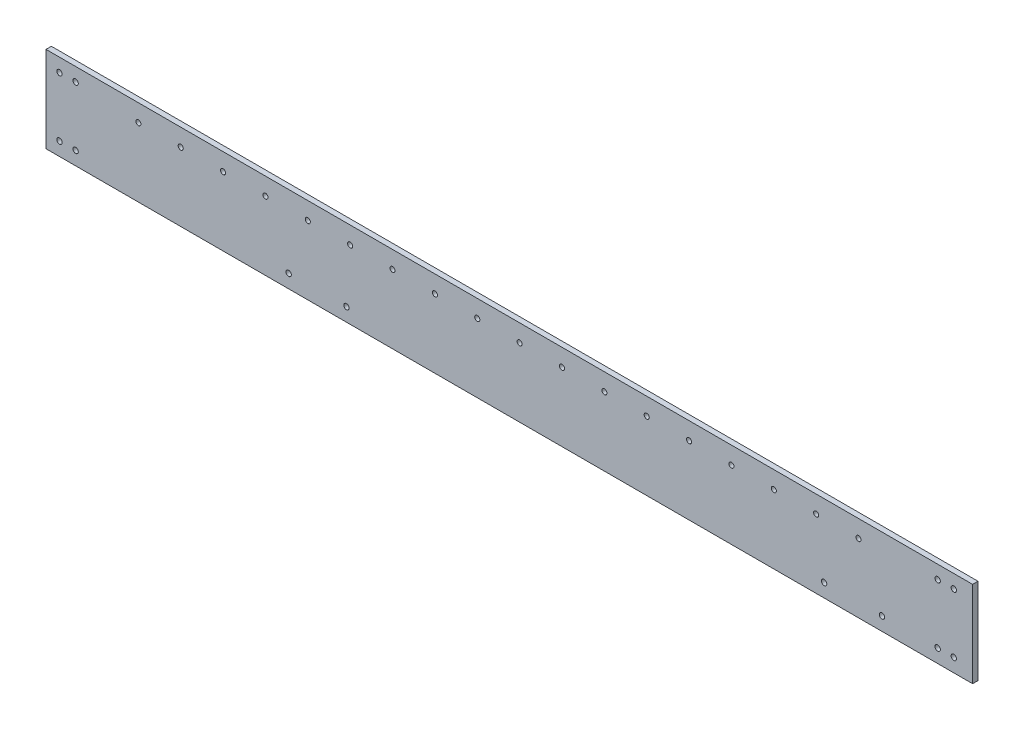
SolidWorks part; units mm, degrees
ref_plane "Front Plane" through (0, 0, 0) normal (0, 0, 1) x (1, 0, 0)
ref_plane "Top Plane" through (0, 0, 0) normal (0, 1, 0) x (1, 0, 0)
ref_plane "Right Plane" through (0, 0, 0) normal (1, 0, 0) x (0, 0, -1)
sketch "Sketch1" plane through (0, 0, 0) normal (1, 0, 0) x (0, 0, -1)
  line L0 (0, 0) -> (-3.175, 0)
  line L3 (-3.175, 0) -> (-3.175, 50.8)
  line L4 (-3.175, 50.8) -> (0, 50.8)
  line L5 (0, 50.8) -> (0, 0)
  dimension "LHeight" = 50.8
  dimension "LMaterialThickness" = 3.175
extrude "Boss-Extrude1" add sketch "Sketch1" along normal blind 546.825
sketch "SideHoles-Sketch4" plane through (0, 0, 3.175) normal (0, 0, 1) x (1, 0, 0)
  line L1 (546.825, 50.8) -> (546.825, 0) construction
  line L2 (0, 50.8) -> (0, 0) construction
  line L3 (546.825, 50.8) -> (0, 50.8) construction
  line L4 (546.825, 0) -> (0, 0) construction
  line L5 (546.825, 50.8) -> (0, 50.8) construction
  line L6 (0, 50.8) -> (0, 0) construction
  line L7 (546.825, 50.8) -> (546.825, 0) construction
  circle A1 centre (7.9375, 42.8625) radius 1.5875
  circle A3 centre (526.1875, 42.8625) radius 1.5875
  circle A4 centre (17.4625, 42.8625) radius 1.5875
  circle A5 centre (535.7125, 42.8625) radius 1.5875
  circle A6 centre (7.9375, 7.9375) radius 1.5875
  circle A7 centre (17.4625, 7.9375) radius 1.5875
  circle A8 centre (526.1875, 7.9375) radius 1.5875
  circle A9 centre (535.7125, 7.9375) radius 1.5875
  circle A10 centre (54.5, 40.575) radius 1.5
  circle A11 centre (79.5, 40.575) radius 1.5
  circle A12 centre (104.5, 40.575) radius 1.5
  circle A13 centre (129.5, 40.575) radius 1.5
  circle A14 centre (154.5, 40.575) radius 1.5
  circle A15 centre (179.5, 40.575) radius 1.5
  circle A16 centre (204.5, 40.575) radius 1.5
  circle A17 centre (229.5, 40.575) radius 1.5
  circle A18 centre (254.5, 40.575) radius 1.5
  circle A19 centre (279.5, 40.575) radius 1.5
  circle A20 centre (304.5, 40.575) radius 1.5
  circle A21 centre (329.5, 40.575) radius 1.5
  circle A22 centre (354.5, 40.575) radius 1.5
  circle A23 centre (379.5, 40.575) radius 1.5
  circle A24 centre (493.3125, 7.9375) radius 1.5875
  circle A26 centre (177.3125, 7.9375) radius 1.5875
  circle A29 centre (404.5, 40.575) radius 1.5
  circle A30 centre (429.5, 40.575) radius 1.5
  circle A31 centre (454.5, 40.575) radius 1.5
  circle A32 centre (479.5, 40.575) radius 1.5
  circle A34 centre (143.1875, 7.9375) radius 1.5875
  circle A36 centre (459.1875, 7.9375) radius 1.5875
  point P60 (0, 0)
  point P61 (0, 0)
  point P62 (0, 0)
  point P63 (0, 0)
  point P78 (0, 0)
  dimension "D2" = 3.175
  dimension "D10" = 3
  dimension "D14" = 3.175
  dimension "D4" = 7.9375
  dimension "D3" = 11.1125
  dimension "D5" = 20.6375
  dimension "D1" = 7.9375
  dimension "D6" = 17.4625
  dimension "D7" = 7.9375
  dimension "D9" = 10.225
  dimension "D8" = 54.5
  dimension "D12" = 25
  dimension "D15" = 7.9375
  dimension "D17" = 53.5125
  dimension "D18" = 316
  dimension "D13" = 34.125
  dimension "D16" = 34.125
  dimension "D11" = 18
extrude "SideHoles-Cut-Extrude3" cut sketch "SideHoles-Sketch4" against normal through all
equation "\"MidLeftOrRightSideRailHeight\"= 2.0in"
equation "\"RailThickness\"= .125in'Spec"
equation "\"SideRailHoleY1FromEdge\"= \"HoleOffsetFromEdge\""
equation "\"SideRailHoleX1FromSide\"= \"HoleOffsetFromSide\""
equation "\"MidSideRailLength\"= \"SideRailLength\" - \"RailThickness\"'Equals 546.825 => MidSideRail buts up against MidBackRail"
equation "\"VSWidth\"= 1.25in'Spec"
equation "\"HoleOffsetFromEdge\"= \"RailThickness\" * 2.5"
equation "\"HoleOffsetFromSide\"= \"RailThickness\" * 3.5"
equation "\"SideRailHoleX2FromSide\"= \"VSWidth\" - \"HoleOffsetFromEdge\" - \"RailThickness\"'Equals 20.6375"
equation "\"FasteningHoleDiameter\"= .125in"
equation "\"StepperWidth\"= 42mm'Spec"
equation "\"D2@SideHoles-Sketch4\"=\"FasteningHoleDiameter\""
equation "\"LHeight@Sketch1\"=\"MidLeftOrRightSideRailHeight\""
equation "\"LMaterialThickness@Sketch1\"=\"RailThickness\""
equation "\"D1@Boss-Extrude1\"=\"MidSideRailLength\""
equation "\"D4@SideHoles-Sketch4\"=\"SideRailHoleY1FromEdge\""
equation "\"D3@SideHoles-Sketch4\"=\"SideRailHoleX1FromSide\" "
equation "\"D5@SideHoles-Sketch4\"=\"SideRailHoleX2FromSide\" "
equation "\"D1@SideHoles-Sketch4\"=\"SideRailHoleX1FromSide\" -\"RailThickness\""
equation "\"D6@SideHoles-Sketch4\"=\"SideRailHoleX2FromSide\"-\"RailThickness\""
equation "\"LinearRailXMountHole\"= \"StepperWidth\" + \"LinearRailFirstHoleOffsetFromEdge\""
equation "\"D9@SideHoles-Sketch4\"=\"V6.3 GantryMiddleToToTopOfMidSideRail\""
equation "\"D8@SideHoles-Sketch4\"=\"LinearRailXMountHole\""
equation "\"LinearRailHoleDistance\"= 25mm'Spec"
equation "\"D12@SideHoles-Sketch4\"=\"LinearRailHoleDistance\""
equation "\"SideRailLength\"= 550mm"
equation "\"LinearRailFirstHoleOffsetFromEdge\"= 12.5mm'Spec"
equation "\"D7@SideHoles-Sketch4\"= \"MidRailRodStabilizerMountingHoleOffsetFromEdge\""
equation "\"DistanceFromBedFrontToFirstLeftStepperHole\"= \"LeadScrewNutPadSize\" + 10mm'Equals 34"
equation "\"BeltTensionerDepth\"= \"BeltTensionerBackWallThickness\" + \"BeltTensionerInnerDepth\"'Equals 23.4"
equation "\"20TGT2PulleyDiameter\"= 17.9mm'Spec"
equation "\"BeltTensionerSpaceBetweenPulleyAndWall\"= 1.5mm"
equation "\"BeltTensionerBackWallThickness\"= 4mm"
equation "\"BeltTensionerInnerDepth\"= \"20TGT2PulleyDiameter\" + \"BeltTensionerSpaceBetweenPulleyAndWall\""
equation "\"DistanceFromFrontSideToBedFront\"= \"RailThickness\" + \"BeltTensionerDepth\" + 10mm'Equals 36.575"
equation "\"DistanceBetweenFrontToBackStepperHoles\"= \"BedLength\" - \"DistanceFromBedFrontToFirstLeftStepperHole\"'Equals 316"
equation "\"BedLength\"= \"BedInnerSquareLength\" + \"BedLWidth\" * 2 - \"BedOverlap\" * 2 + \"BedIncreasedByLength\"'Equals 350"
equation "\"BedOverlap\"= 20mm"
equation "\"BedThirdSize\"= 70mm"
equation "\"BedInnerSquareWidth\"= \"BedThirdSize\" * 3'Equals 210"
equation "\"BedLWidth\"= \"BedThirdSize\" + \"BedOverlap\"'Equals 90"
equation "\"BedIncreasedByLength\"= 0mm"
equation "\"LM8UUDiameter\"= 15mm"
equation "\"RodStabilizerDepth\"= \"LM8UUDiameter\" * 2"
equation "\"D14@SideHoles-Sketch4\"= \"FasteningHoleDiameter\""
equation "\"D15@SideHoles-Sketch4\"= \"HoleOffsetFromEdge\""
equation "\"BedInnerSquareLength\"= \"BedInnerSquareWidth\""
equation "\"GABMidWallHeight\"= 28mm'Must equal 28 or changes alignment"
equation "\"20TGT2PulleyWidth\"= 8.7mm'The STL of the Pulley in the diagram is a bit larger"
equation "\"GABMidShortRiserHeight\"= \"GABMidWallHeight\" / 2 - \"20TGT2PulleyWidth\"'Equals 5.3"
equation "\"GABUpperHeight\"= 6mm"
equation "\"GABLowerHeight\"= 3mm"
equation "\"GABRiserBossOffset\"= 0.8mm'Aligns Pulleys"
equation "\"GABHeight\"= \"GABLowerHeight\" + \"GABMidWallHeight\" + \"GABUpperHeight\""
equation "\"StepperShaftLength\"= 24mm'Pulley will be attached to the end"
equation "\"V6.1 FromGantryPulleyToGantryMiddle\"= \"GABHeight\" / 2 - \"GABMidShortRiserHeight\" - \"GABLowerHeight\" + \"GABRiserBossOffset\" / 2"
equation "\"V6.2 GantryMiddleToTopOfMidBackRail\"= \"StepperShaftLength\" - \"V6.1 FromGantryPulleyToGantryMiddle\""
equation "\"V6.3 GantryMiddleToToTopOfMidSideRail\"= \"V6.2 GantryMiddleToTopOfMidBackRail\" - \"RailThickness\""
equation "\"DistanceFromFrontSideToFirstLeftStabilizerMountingHole\"= \"DistanceFromFrontSideToFirstLeftStepperHole\" - \"DistanceFromStepperHoleToRodStabilizerMountingHole\"'Equals 53.5125"
equation "\"DistanceFromFrontSideToFirstLeftStepperHole\"= \"DistanceFromFrontSideToBedFront\" + \"DistanceFromBedFrontToFirstLeftStepperHole\"'Equals 70.575"
equation "\"LeadScrewNutMountingHoleFlangeDiameter\"= 22mm'Spec"
equation "\"LeadScrewNutPadSize\"= \"LeadScrewNutMountingHoleFlangeDiameter\" + 2mm'Equals 24"
equation "\"D17@SideHoles-Sketch4\"=\"DistanceFromFrontSideToFirstLeftStabilizerMountingHole\""
equation "\"D18@SideHoles-Sketch4\"=\"DistanceBetweenFrontToBackStepperHoles\""
equation "\"MidRailRodStabilizerMountingHoleOffsetFromEdge\"= \"HoleOffsetFromEdge\""
equation "\"RodStabilizerMountingHoleOffsetInsideX\"= 14.125mm'Backward compatible"
equation "\"RodStabilizerMountingHoleOffsetOutsideX\"= 12mm"
equation "\"RodStabilizerLength\"= 50mm"
equation "\"DistanceFromStepperHoleToRodStabilizerMountingHole\"= \"RodStabilizerLength\" / 2 - \"HoleOffsetFromEdge\"'Equals 17.0625"
equation "\"D13@SideHoles-Sketch4\"=\"RodStabilizerLength\" - \"HoleOffsetFromEdge\" * 2"
equation "\"D16@SideHoles-Sketch4\"=\"RodStabilizerLength\" - \"HoleOffsetFromEdge\" *2"
